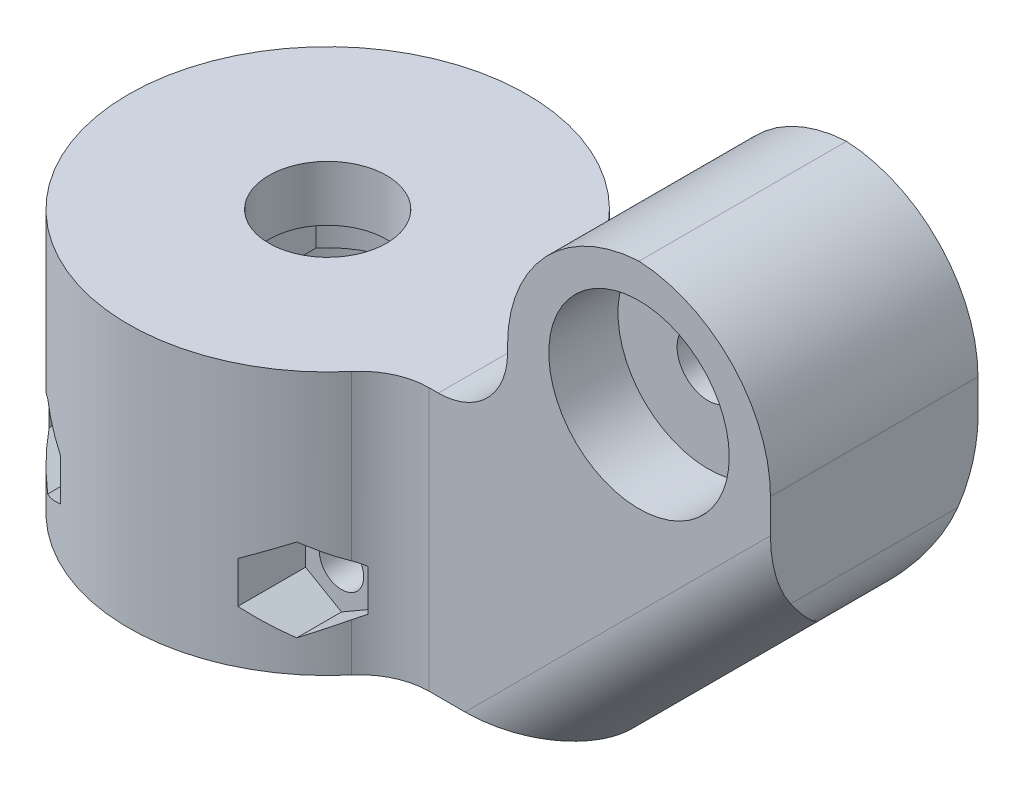
SolidWorks part; units mm, degrees
ref_plane "Front Plane" through (0, 0, 0) normal (0, 0, 1) x (1, 0, 0)
ref_plane "Top Plane" through (0, 0, 0) normal (0, 1, 0) x (1, 0, 0)
ref_plane "Right Plane" through (0, 0, 0) normal (1, 0, 0) x (0, 0, -1)
sketch "Sketch1" plane through (0, 0, 0) normal (0, 0, 1) x (1, 0, 0)
  line L0 (-9.5, 9) -> (9.5, 9)
  line L1 (9.5, 9) -> (9.5, -10.52)
  line L2 (-5.5, -25.52) -> (-30, -25.52)
  line L3 (-30, -25.52) -> (-30, -6.52)
  line L4 (-30, -6.52) -> (-9.5, -6.52)
  line L5 (-9.5, -6.52) -> (-9.5, 9)
  line L6 (-16.2026, -6.52) -> (19.4501, -6.52) construction
  line L7 (9.5, -10.52) -> (-5.5, -25.52)
  circle A0 centre (0, 0) radius 2.25
  circle A1 centre (0, 0) radius 6.52
  point P5 (9.5, -25.52)
  point P10 (0, 9)
  dimension "D1" = 4.5
  dimension "D4" = 13.04
  dimension "D2" = 19
  dimension "D3" = 9
  dimension "D5" = 30
  dimension "D7" = 19
extrude "Boss-Extrude1" add sketch "Sketch1" along normal mid plane 15 contours L6 L4 L3 L2 L1 | L5 L6 A1 L1 L0 | A1 A0 region at (-4.4799, 4.4799, 0) region at (0, 8.7547, 0) region at (-12.8509, -15.2265, 0)
extrude "Cut-Extrude1" cut sketch "Sketch1<3>" against normal blind 5 from surface contours A1 starting at face at (-9.3571, -8.0857, 7.5)
sketch "Sketch1<3>" plane through (0, 0, 0) normal (0, 0, 1) x (1, 0, 0) same geometry as "Sketch1"
extrude "Cut-Extrude2" cut sketch "Sketch1<4>" along normal blind 5 from surface contours A1 starting at face at (-9.3571, -8.0857, -7.5)
sketch "Sketch1<4>" plane through (0, 0, 0) normal (0, 0, 1) x (1, 0, 0) same geometry as "Sketch1"
sketch "Sketch2" plane through (0, -6.52, 0) normal (0, 1, 0) x (1, 0, 0)
  line L0 (-30, -7.5) -> (-30, 7.5) construction
  circle A0 centre (-30, 0) radius 11.4
  circle A1 centre (-30, 0) radius 4.25
  circle A2 centre (-30, 0) radius 14.4
  line M2 (-30, 7.5) -> (-30, -7.5)
  dimension "D1" = 22.8
  dimension "D2" = 8.5
  dimension "D3" = 3
extrude "Boss-Extrude2" add sketch "Sketch2" against normal through all contours A2
extrude "Cut-Extrude3" cut sketch "Sketch2<3>" against normal through all both and the other way through all contours A1 M2 | A1 M2 region at (-28.1962, -6.52, 0) region at (-31.8038, -6.52, 0)
sketch "Sketch2<3>" plane through (0, -6.52, 0) normal (0, 1, 0) x (1, 0, 0) same geometry as "Sketch2"
fillet "Fillet1" radius 5 3 edges at (-17.7073, -16.02, -7.5) (-9.5, -6.52, 0) (-17.7073, -16.02, 7.5)
fillet "Fillet2" radius 10 2 edges at (-9.5, 9, 0) (9.5, 9, 0)
sketch "Sketch4" plane through (0, -25.52, 0) normal (0, -1, 0) x (1, 0, 0)
  line L0 (-30, -1000) -> (-30, 16.7965) construction
  line L1 (-25, -4.1533) -> (-25, 4.1533)
  line L2 (-35, -4.1533) -> (-35, 4.1533)
  line L3 (-35, -1000) -> (-35, 16.7965) construction
  line L4 (-25, -1000) -> (-25, 16.7965) construction
  arc A0 (-35, -4.1533) -> (-25, -4.1533) centre (-30, 0) ccw
  arc A1 (-25, 4.1533) -> (-35, 4.1533) centre (-30, 0) ccw
  dimension "D1" = 13
  dimension "D2" = 5
  dimension "D3" = 5
extrude "Cut-Extrude6" cut sketch "Sketch4" against normal offset from surface (15 mm away) 4 up to face at (-30, -6.52, 4.25)
sketch "Sketch5" plane through (0, -25.52, 0) normal (0, -1, 0) x (1, 0, 0)
  circle A0 centre (-30, 0) radius 8.1
  dimension "D1" = 16.2
extrude "Cut-Extrude7" cut sketch "Sketch5" against normal blind 12
sketch "Sketch6" plane through (0, 0, 0) normal (0, 0, 1) x (1, 0, 0)
  line L2 (-35, -10.52) -> (-25, -10.52) construction
  line L3 (-38.1, -13.52) -> (-21.9, -13.52) construction
  line L5 (-38.1, -25.52) -> (-38.1, -13.52) construction
  line L6 (-30, -13.52) -> (-30, -19.52) construction
  line L7 (-23.5981, -21.72) -> (-23.5981, -18.72)
  line L8 (-39, -17.22) -> (-41.5981, -18.72)
  line L9 (-41.5981, -18.72) -> (-41.5981, -21.72)
  line L10 (-41.5981, -21.72) -> (-39, -23.22)
  line L11 (-39, -23.22) -> (-36.4019, -21.72)
  line L12 (-36.4019, -21.72) -> (-36.4019, -18.72)
  line L13 (-36.4019, -18.72) -> (-39, -17.22)
  line L14 (-21, -23.22) -> (-23.5981, -21.72)
  line L15 (-18.4019, -21.72) -> (-21, -23.22)
  line L16 (-18.4019, -18.72) -> (-18.4019, -21.72)
  line L17 (-21, -17.22) -> (-18.4019, -18.72)
  line L18 (-23.5981, -18.72) -> (-21, -17.22)
  circle A0 centre (-39, -20.22) radius 1.6
  circle A2 centre (-39, -20.22) radius 3 construction
  circle A3 centre (-21, -20.22) radius 1.6
  circle A4 centre (-39, -20.22) radius 3.5
  circle A5 centre (-21, -20.22) radius 3.5
  point P29 (-30, -10.52)
  dimension "D1" = 3.2
  dimension "D3" = 6
  dimension "D4" = 7
  dimension "D2" = 9
  dimension "D5" = 6.7
extrude "Cut-Extrude8" cut sketch "Sketch6" against normal through all both and the other way through all contours A0 | A3
extrude "Cut-Extrude9" cut sketch "Sketch6<3>" along normal blind 12 from offset 8 contours L12 L13 L8 L9 L10 L11 A0 | L18 L7 L14 L15 L16 L17 A3 region at (-23.5187, -20.22, 0) region at (-37.7406, -18.0387, 0)
sketch "Sketch6<3>" plane through (0, 0, 0) normal (0, 0, 1) x (1, 0, 0) same geometry as "Sketch6"
extrude "Cut-Extrude10" cut sketch "Sketch6<4>" against normal blind 12 from offset 9 contours A4 | A5 offset against normal yes
sketch "Sketch6<4>" plane through (0, 0, 0) normal (0, 0, 1) x (1, 0, 0) same geometry as "Sketch6"
fillet "Fillet3" radius 5 3 edges at (2, -18.02, 7.5) (2, -18.02, -7.5) (9.5, -10.52, 0)
